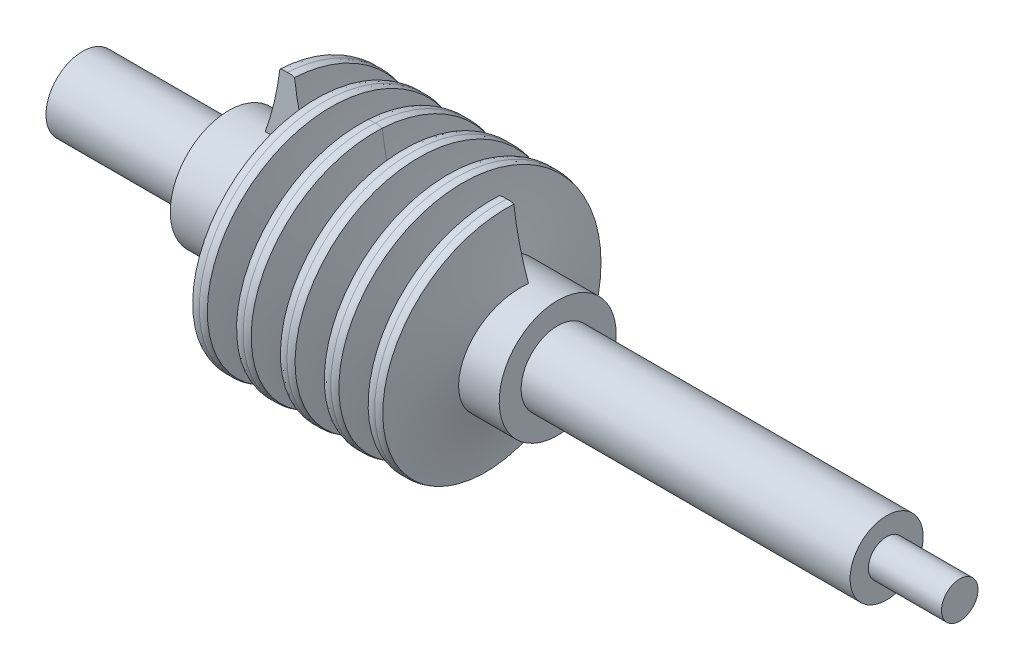
SolidWorks part; units mm, degrees
note: The reader was unsure of these and kept them because the rebuilt part matched: shared geometry of "Sketch3<2>".
ref_plane "Front Plane" through (0, 0, 0) normal (0, 0, 1) x (1, 0, 0)
ref_plane "Top Plane" through (0, 0, 0) normal (0, 1, 0) x (1, 0, 0)
ref_plane "Right Plane" through (0, 0, 0) normal (1, 0, 0) x (0, 0, -1)
sketch "Sketch1" plane through (0, 0, 0) normal (0, 0, 1) x (1, 0, 0)
  line L0 (0, 0) -> (0, 5)
  line L1 (0, 5) -> (20, 5)
  line L2 (20, 5) -> (20, 8)
  line L3 (20, 8) -> (65, 8)
  line L4 (65, 8) -> (65, 5)
  line L5 (65, 5) -> (110, 5)
  line L6 (110, 5) -> (110, 2.5)
  line L7 (110, 2.5) -> (120, 2.5)
  line L8 (120, 2.5) -> (120, 0)
  line L9 (120, 0) -> (0, 0)
  dimension "D1" = 120
  dimension "D2" = 20
  dimension "D3" = 10
  dimension "D4" = 45
  dimension "D5" = 2.5
  dimension "D6" = 5
  dimension "D7" = 8
  dimension "D8" = 5
revolve "Revolve1" add sketch "Sketch1" angle 360 about L9
ref_plane "Plane1" through (40, 0, 0) normal (1, 0, 0) x (0, 0, -1)
sketch "Sketch2" plane through (40, 0, 0) normal (1, 0, 0) x (0, 0, -1)
  circle A0 centre (0, 0) radius 8 construction
  circle A1 centre (0, 0) radius 8
curve "Helix/Spiral1" pitch 6 height 12 turns 2
sketch "Sketch3" plane through (0, 0, 0) normal (0, 0, 1) x (1, 0, 0)
  line L0 (40, 8) -> (40, 16.5) construction
  line L1 (65, 8) -> (20, 8) construction
  line L2 (40, -18.219) -> (40, 18.219) construction
  line L3 (43, 6) -> (37, 6)
  line L4 (37, 6) -> (37, 8)
  line L5 (43, 6) -> (43, 8)
  arc A0 (37, 8) -> (39, 16.4) centre (0.2938, 21.1777) ccw
  arc A1 (39, 16.4) -> (40, 16.5) centre (39.672, 14.7301) cw
  arc A2 (41, 16.4) -> (40, 16.5) centre (40.328, 14.7301) ccw
  arc A3 (43, 8) -> (41, 16.4) centre (79.7062, 21.1777) cw
  spline S0 degree 3 poles (40, 8) (39.8758, 8) (39.6246, 7.5835) (39.2501, 5.8041) (38.875, 3.1412) (38.5, 0) (38.125, -3.1412) (37.75, -5.8041) (37.375, -7.5835) (37, -8.2083) (36.625, -7.5835) (36.25, -5.8041) (35.875, -3.1412) (35.5, 0) (35.125, 3.1412) (34.75, 5.8041) (34.375, 7.5835) (34, 8.2083) (33.625, 7.5835) (33.25, 5.8041) (32.875, 3.1412) (32.5, 0) (32.125, -3.1412) (31.75, -5.8041) (31.375, -7.5835) (31, -8.2083) (30.625, -7.5835) (30.25, -5.8041) (29.875, -3.1412) (29.5, 0) (29.125, 3.1412) (28.7499, 5.8041) (28.3754, 7.5835) (28.1242, 8) (28, 8) knots 0 0 0 0 0.03125 0.0625 0.09375 0.125 0.15625 0.1875 0.21875 0.25 0.28125 0.3125 0.34375 0.375 0.40625 0.4375 0.46875 0.5 0.53125 0.5625 0.59375 0.625 0.65625 0.6875 0.71875 0.75 0.78125 0.8125 0.84375 0.875 0.90625 0.9375 0.96875 1 1 1 1 construction
  point P44 (40, 6)
  dimension "D1" = 3
  dimension "D3" = 39
  dimension "D4" = 1.8
  dimension "D2" = 2
  dimension "D5" = 8.5
  dimension "D6" = 1
  dimension "D7" = 0.1
sweep "Sweep1" add profiles "Sketch3" path "Helix/Spiral1"
sketch "Sketch4" plane through (40, 0, 0) normal (1, 0, 0) x (0, 0, -1)
  circle A0 centre (0, 0) radius 8 construction
  circle A1 centre (0, 0) radius 8
curve "Helix/Spiral2" pitch 6 height 18 turns 3
sweep "Sweep2" add profiles "Sketch3<2>" path "Helix/Spiral2"
sketch "Sketch3<2>" plane through (0, 0, 0) normal (0, 0, 1) x (1, 0, 0) same geometry as "Sketch3"
